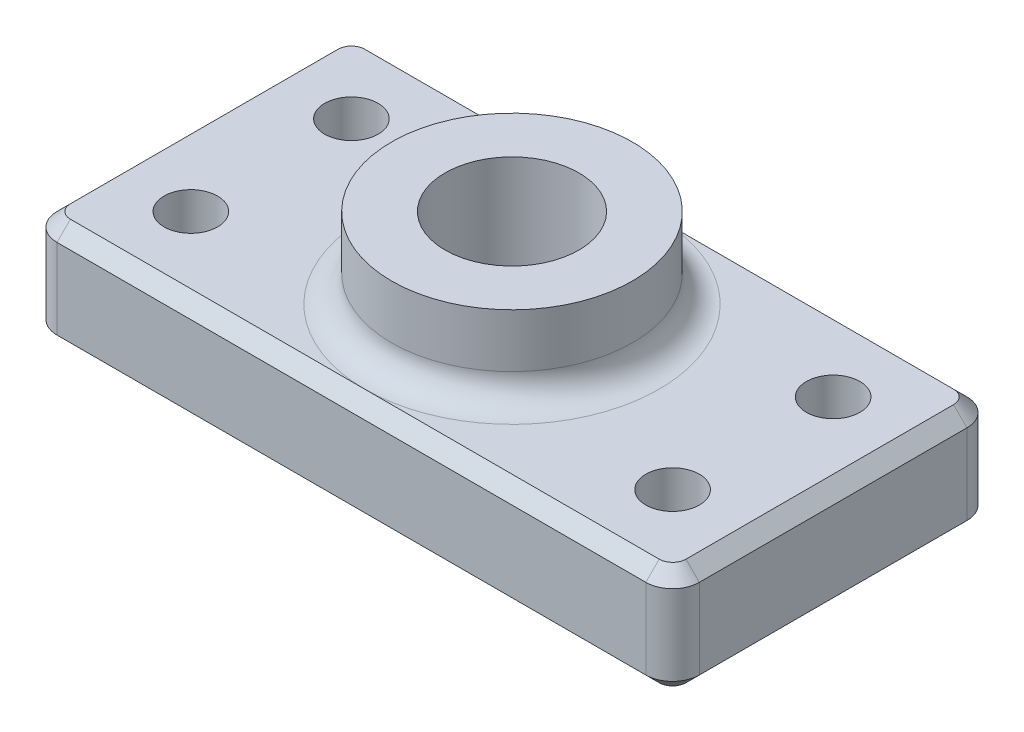
SolidWorks part; units mm, degrees
ref_plane "Front Plane" through (0, 0, 0) normal (0, 0, 1) x (1, 0, 0)
ref_plane "Top Plane" through (0, 0, 0) normal (0, 1, 0) x (1, 0, 0)
ref_plane "Right Plane" through (0, 0, 0) normal (1, 0, 0) x (0, 0, -1)
sketch "Sketch1" plane through (0, 0, 0) normal (0, 1, 0) x (1, 0, 0)
  line L1 (-3, 1.5) -> (3, 1.5)
  line L2 (-3, 1.5) -> (-3, -1.5)
  line L3 (-3, -1.5) -> (3, -1.5)
  line L4 (3, 1.5) -> (3, -1.5)
  line L5 (-3, 1.5) -> (3, -1.5) construction
  line L6 (-3, -1.5) -> (3, 1.5) construction
  point P0 (0, 0)
  dimension "D1" = 3
  dimension "D2" = 6
extrude "Boss-Extrude1" add sketch "Sketch1" along normal blind 1
sketch "Sketch3" plane through (0, 1, 0) normal (0, 1, 0) x (1, 0, 0)
  circle A0 centre (0, 0) radius 1.125
  dimension "D1" = 2.25
extrude "Boss-Extrude3" add sketch "Sketch3" along normal blind 0.75
sketch "Sketch5" plane through (0, 0, 0) normal (0, 1, 0) x (1, 0, 0)
  circle A0 centre (0, 0) radius 0.625
  dimension "D1" = 1.25
extrude "Cut-Extrude3" cut sketch "Sketch5" along normal through all
fillet "Fillet1" radius 0.25 1 edges at (0, 1, 1.125)
sketch "Sketch6" plane through (0, 1, 0) normal (0, 1, 0) x (1, 0, 0)
  line L0 (3, -1.5) -> (3, 1.5) construction
  line L1 (3, 1.5) -> (-3, 1.5) construction
  line L2 (-3, -1.5) -> (3, -1.5) construction
  line L3 (-3, 1.5) -> (-3, -1.5) construction
  circle A0 centre (2.25, -0.75) radius 0.25
  circle A1 centre (2.25, 0.75) radius 0.25
  circle A2 centre (-2.25, 0.75) radius 0.25
  circle A3 centre (-2.25, -0.75) radius 0.25
  point P12 (3.7241, 0.9485)
  point P17 (-3.5466, 0.1815)
  dimension "D9" = 0.5
  dimension "D1" = 0.75
  dimension "D2" = 0.75
  dimension "D3" = 0.75
  dimension "D4" = 0.75
  dimension "D5" = 0.75
  dimension "D6" = 0.75
  dimension "D7" = 0.75
  dimension "D8" = 0.75
extrude "Cut-Extrude4" cut sketch "Sketch6" against normal through all
fillet "Fillet3" radius 0.25 4 edges at (3, 0.5, -1.5) (3, 0.5, 1.5) (-3, 0.5, 1.5) (-3, 0.5, -1.5)
chamfer "Chamfer2" distance 0.125 angle 45 16 edges at (3, 0, 0) (2.9268, 0, -1.4268) (2.9268, 0, 1.4268) (0, 0, -1.5) (0, 0, 1.5) (-2.9268, 0, -1.4268) (-2.9268, 0, 1.4268) (-3, 0, 0) (0, 1, -1.5) (-2.9268, 1, -1.4268) (2.9268, 1, -1.4268) (-3, 1, 0) (3, 1, 0) (-2.9268, 1, 1.4268) (2.9268, 1, 1.4268) (0, 1, 1.5)
